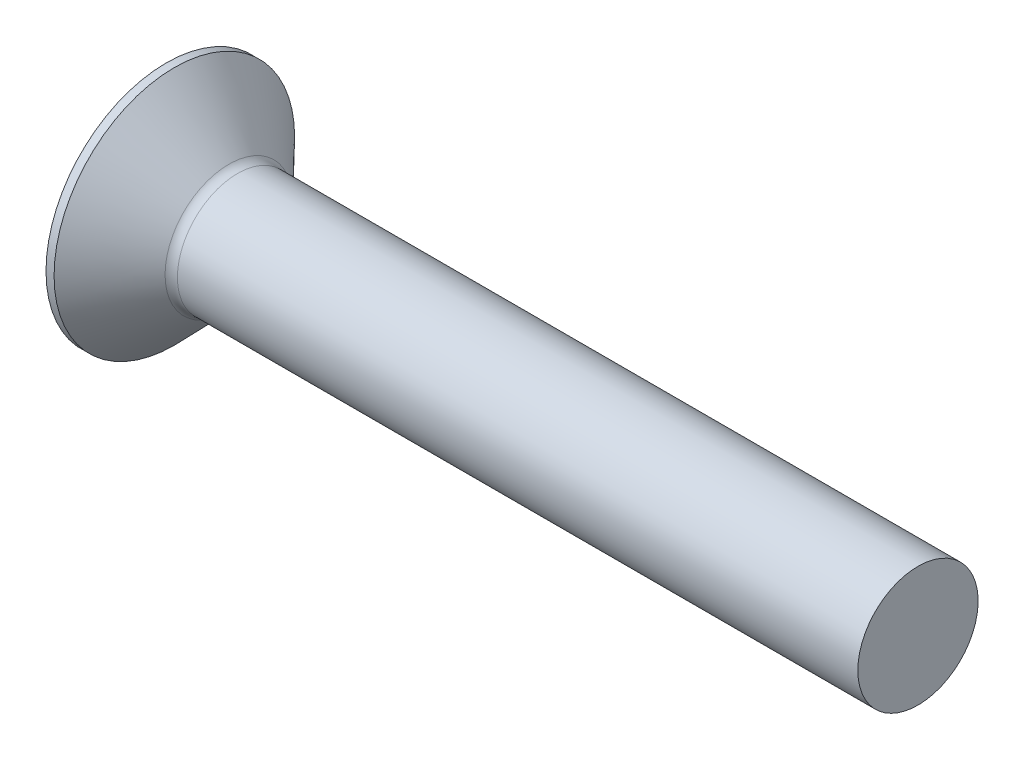
SolidWorks part; units mm, degrees
ref_plane "Front Plane" through (0, 0, 0) normal (0, 0, 1) x (1, 0, 0)
ref_plane "Top Plane" through (0, 0, 0) normal (0, 1, 0) x (1, 0, 0)
ref_plane "Right Plane" through (0, 0, 0) normal (1, 0, 0) x (0, 0, -1)
sketch "BodySke" plane through (0, 0, 0) normal (0, 0, 1) x (1, 0, 0)
  line L0 (0, 0) -> (111.3824, 0) construction
  line L1 (0, 0) -> (0, 8)
  line L2 (0, 8) -> (0.5372, 8)
  line L3 (0.5372, 8) -> (4.4, 4)
  line L4 (4.4, 4) -> (50, 4)
  line L5 (50, 4) -> (50, 0)
  line L6 (5.65, 7.824) -> (5.65, -6.8939) construction
  line L7 (0, 0) -> (50, 0)
  line L8 (20, 8.824) -> (20, -4.958) construction
  line L9 (0, -8) -> (0.5372, -8) construction
  line L10 (0.5372, -8) -> (4.4, -4) construction
  line L11 (4.4, -4) -> (50, -4) construction
  point P10 (50, 3.4455)
  dimension "Thread_minor" = 6.891
  dimension "Length" = 50
  dimension "Head_height" = 4.4
  dimension "Head_dia" = 16
  dimension "Advance" = 1.25
revolve "BaseBody" add sketch "BodySke" angle 360 about L0
cosmetic thread "ThreadCosmetic" [suppressed] parameters "Thread_minor"=6.891
fillet "Fillet1" radius 0.8 1 edges at (4.4, 0, 4)
ref_plane "Plane1" through (4.96, 0, 0) normal (1, 0, 0) x (0, 0, -1)
sketch "RecSkeTop" plane through (0, 0, 0) normal (-1, 0, 0) x (0, 0, 1)
  line L1 (-0.924, 4.2) -> (0.924, 4.2)
  line L2 (-0.924, 4.2) -> (-0.924, -4.2)
  line L3 (-0.924, -4.2) -> (0.924, -4.2)
  line L4 (0.924, 4.2) -> (0.924, -4.2)
  dimension "D1" = 4.2
  dimension "D2" = 1.848
  dimension "D3" = 0.924
sketch "RecSkeBot" plane through (4.96, 0, 0) normal (1, 0, 0) x (0, 0, -1)
  line L0 (0.924, 4.2) -> (0.924, -4.2) construction
  line L1 (0.924, 1.727) -> (-0.924, 1.727)
  line L2 (0.924, 1.727) -> (0.924, -1.727)
  line L3 (0.924, -1.727) -> (-0.924, -1.727)
  line L4 (-0.924, 1.727) -> (-0.924, -1.727)
  line L5 (-0.924, 4.2) -> (-0.924, -4.2) construction
  dimension "D1" = 3.4541
  dimension "D2" = 1.727
loft "Recess" cut profiles "RecSkeTop", "RecSkeBot" connector at (0, -4.2, 0.924) connector at (4.96, -1.727, 0.924)
pattern_circular "RecPat" count 2 every 90 about axis through (0, 0, 0) along (1, 0, 0) of "Recess"
sketch "RecCorSke" plane through (0, 0, 0) normal (0, 0, 1) x (1, 0, 0)
  line L0 (0, 0) -> (57.5987, 0) construction
  line L1 (0, 0) -> (0, 2.0328)
  line L2 (0, 8) -> (0, -8) construction
  line L3 (0, 2.0328) -> (4.96, 1.686)
  line L4 (4.96, 1.686) -> (5.5078, 0)
  line L5 (5.5078, 0) -> (0, 0)
  dimension "D1" = 18
  dimension "D2" = 4.96
  dimension "D3" = 2.0328
  dimension "D4" = 4
revolve "RecessCore" cut sketch "RecCorSke" angle 360 about L0
sketch "ThdSchSke" plane through (0, 0, 0) normal (0, 0, 1) x (1, 0, 0)
  line L0 (0, 0) -> (55.1256, 0) construction
  line L1 (0, 0) -> (111.3824, 0) construction
  line L2 (49.6799, 4) -> (49.6799, 4.6403)
  line L3 (49.6799, 4.6403) -> (50.3201, 4.6403)
  line L4 (50.3201, 4.6403) -> (50.3201, 4)
  line L5 (50.3201, 4) -> (50, 3.4455)
  line L6 (50, 3.4455) -> (49.6799, 4)
  line L7 (4.4, 4) -> (50, 4) construction
  line L13 (50, 4) -> (50, 0) construction
revolve "ThreadSchematic" [suppressed] cut sketch "ThdSchSke" angle 360 about L0
pattern_linear "ThdSchPat" [suppressed] count 24 along (-1, 0, 0) of bodies 103
equation "\"Thread_minor@ThreadCosmetic\" = \"Thread_minor@BodySke\""
equation "\"D1@RecSkeTop\" = \"Cross_dia@RecSkeTop\" / 2"
equation "\"D2@RecSkeTop\" = \"Cross_dia@RecSkeTop\" * 0.22"
equation "\"D3@RecSkeTop\" = \"D2@RecSkeTop\" / 2"
equation "\"D1@RecSkeBot\" = \"Cross_dia@RecSkeTop\" - 2 * \"Cross_depth@Plane1\" *  tan( 26.5 * 0.017453292 ) "
equation "\"D2@RecSkeBot\" = \"D1@RecSkeBot\" / 2"
equation "\"D2@RecCorSke\" = \"Cross_depth@Plane1\""
equation "\"D3@RecCorSke\" = \"D2@RecSkeTop\" * 1.1"
equation "\"Advance@ThdSchPat\" = \"Advance@BodySke\""
equation "\"D1@ThdSchPat\" =  int( \"Thread_length@BodySke\" / \"Advance@ThdSchPat\" ) "
